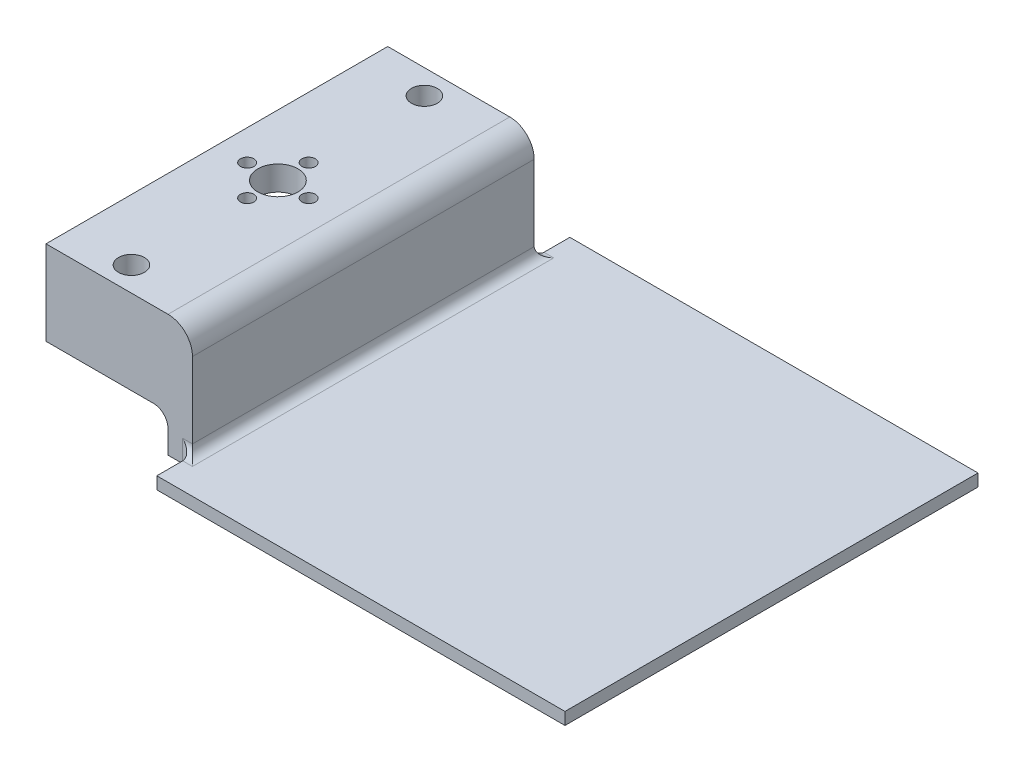
SolidWorks part; units mm, degrees
other "Markup1"
sketch "Sketch16" plane through (-31.975, 25.4, -53.721) normal (0, 1, 0) x (1, 0, 0)
ref_plane "Front Plane" through (0, 0, 0) normal (0, 0, 1) x (1, 0, 0)
ref_plane "Top Plane" through (0, 0, 0) normal (0, 1, 0) x (1, 0, 0)
ref_plane "Right Plane" through (0, 0, 0) normal (1, 0, 0) x (0, 0, -1)
sketch "Sketch1" plane through (0, 0, 0) normal (0, 1, 0) x (1, 0, 0)
  line L1 (0, -53.721) -> (106.172, -53.721)
  line L2 (0, -53.721) -> (0, 53.721)
  line L3 (0, 53.721) -> (106.172, 53.721)
  line L4 (106.172, -53.721) -> (106.172, 53.721)
  point P4 (0, 0)
  dimension "D1" = 107.442
  dimension "D2" = 106.172
extrude "Boss-Extrude1" add sketch "Sketch1" along normal blind 3.175
sketch "Sketch13" plane through (0, 0, 0) normal (0, 1, 0) x (1, 0, 0)
  line L0 (0, 53.721) -> (0, -53.721) construction
  line L1 (0, 44.45) -> (-38.1, 44.45)
  line L2 (0, 44.45) -> (0, -44.45)
  line L3 (0, -44.45) -> (-38.1, -44.45)
  line L4 (-38.1, 44.45) -> (-38.1, -44.45)
  point P9 (0, 0)
  dimension "D1" = 88.9
  dimension "D2" = 38.1
extrude "Boss-Extrude7" add sketch "Sketch13" along normal blind 31.75
sketch "Sketch15" plane through (0, 31.75, 0) normal (0, 1, 0) x (1, 0, 0)
  circle A0 centre (-22.225, -38.1) radius 3.2385 construction
  circle A1 centre (-22.225, 38.1) radius 3.2385 construction
  circle A6 centre (-22.225, -38.1) radius 3.2385 construction
  circle A7 centre (-22.225, 38.1) radius 3.2385 construction
  circle A8 centre (-22.225, 0) radius 2.6905 construction
  circle A9 centre (-22.225, 0) radius 2.6905 construction
  circle A10 centre (-22.225, 38.1) radius 3.3655
  circle A11 centre (-22.225, -38.1) radius 3.3655
  circle A12 centre (-22.225, 0) radius 5.227
  circle A13 centre (-14.225, 0) radius 1.75
  circle A14 centre (-22.225, -8) radius 1.75
  circle A15 centre (-30.225, 0) radius 1.75
  circle A16 centre (-22.225, 8) radius 1.75
  point P23 (-22.225, 0)
  dimension "D1" = 6.731
  dimension "D2" = 10.454
  dimension "D4" = 3.5
  dimension "D3" = 8
  dimension "D5" = 4
extrude "Cut-Extrude1" cut sketch "Sketch15" against normal through all
sketch "Sketch17" plane through (-38.1, 0, 0) normal (-1, 0, 0) x (0, 0, 1)
  line L0 (-44.45, 0) -> (44.45, 0) construction
  line L1 (31.75, 0) -> (-31.75, 0)
  line L2 (31.75, 0) -> (31.75, 25.4)
  line L3 (31.75, 25.4) -> (-31.75, 25.4)
  line L4 (-31.75, 0) -> (-31.75, 25.4)
  line L5 (-44.45, 31.75) -> (44.45, 31.75) construction
  point P6 (0, 0)
  dimension "D1" = 63.5
  dimension "D2" = 6.35
extrude "Cut-Extrude2" cut sketch "Sketch17" against normal offset from surface (31.75 mm away) 6.35 up to face at (0, 17.4625, 0)
sketch "Sketch18" plane through (0, 0, -44.45) normal (0, 0, -1) x (-1, 0, 0)
  line L0 (38.1, 31.75) -> (38.1, 0) construction
  line L1 (38.1, 9.779) -> (6.35, 9.779)
  line L2 (38.1, 9.779) -> (38.1, 0)
  line L3 (38.1, 0) -> (6.35, 0)
  line L4 (6.35, 9.779) -> (6.35, 0)
  line L5 (0, 0) -> (38.1, 0) construction
  line L7 (6.35, 0) -> (38.1, 0) construction
  dimension "D1" = 9.779
extrude "Cut-Extrude3" cut sketch "Sketch18" against normal through all
fillet "Fillet2" radius 12.7 2 edges at (-22.225, 25.4, 31.75) (-22.225, 25.4, -31.75)
fillet "Fillet1" radius 3.81 7 edges at (-6.35, 11.2395, 31.75) (-6.35, 25.4, 0) (-6.35, 11.2395, -31.75) (-6.35, 21.6803, 28.0303) (-6.35, 21.6803, -28.0303) (-6.35, 9.779, -38.1) (-6.35, 9.779, 38.1)
fillet "Fillet3" radius 2.54 1 edges at (0, 3.175, 0)
fillet "Fillet4" radius 2.54 4 edges at (1.27, 3.175, 44.45) (1.27, 3.175, -44.45) (0, 1.5875, 44.45) (0, 1.5875, -44.45)
fillet "Fillet5" radius 6.35 1 edges at (0, 31.75, 0)
equation "\"tightTol\"= 0.005in"
equation "\"normTol\"= 0.01in"
equation "\"looseTol\"= 0.02in"
equation "\"4.250000in-\"= 4.25"
equation "\"D1@Sketch1\"=4.25-\"looseTol\""
equation "\"D2@Sketch1\"=4.2in-\"looseTol\""
equation "\"D1@Sketch15\"=0.25+1.5*\"normTol\""
equation "\"D2@Sketch15\"=10.2mm+\"normTol\""
equation "\"D3@Sketch15\"=8mm"
equation "\"D4@Sketch15\"= 3.5mm"
equation "\"D1@Sketch18\"=0.375+\"normTol\""
